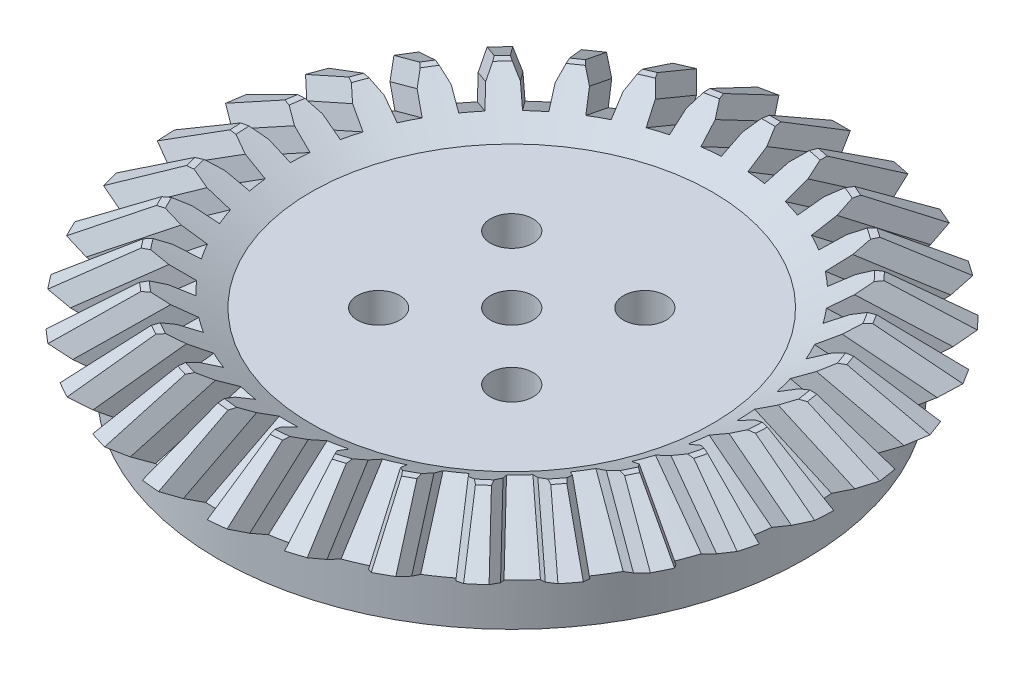
SolidWorks part; units mm, degrees
note: The reader was unsure of these and kept them because the rebuilt part matched: shared geometry of "Sketch13<3>".
ref_plane "Front Plane" through (0, 0, 0) normal (0, 0, 1) x (1, 0, 0)
ref_plane "Top Plane" through (0, 0, 0) normal (0, 1, 0) x (1, 0, 0)
ref_plane "Right Plane" through (0, 0, 0) normal (1, 0, 0) x (0, 0, -1)
sketch "Sketch1" plane through (0, 0, 0) normal (0, 1, 0) x (1, 0, 0)
  line L0 (0, 0) -> (-1.265, 22.0037) construction
  line L1 (0, 0) -> (1.265, 22.0037) construction
  line L2 (-1.265, 22.0037) -> (-1.265, 24.9437)
  line L3 (-1.265, 24.9437) -> (1.265, 24.9437) construction
  line L4 (1.265, 24.9437) -> (1.265, 22.0037)
  line L5 (-1.265, 24.9437) -> (-0.8171, 27.4837)
  line L6 (-0.8171, 27.4837) -> (0.8171, 27.4837)
  line L7 (0.8171, 27.4837) -> (1.265, 24.9437)
  line L8 (6.3328, 26.7566) -> (6.2602, 24.1784)
  line L9 (4.732, 27.0856) -> (6.3328, 26.7566)
  line L10 (3.782, 24.6877) -> (4.732, 27.0856)
  line L11 (3.1902, 21.8079) -> (3.782, 24.6877)
  line L12 (6.2602, 24.1784) -> (5.6684, 21.2986)
  line L13 (11.5893, 24.9341) -> (10.9992, 22.4233)
  line L14 (10.0874, 25.5786) -> (11.5893, 24.9341)
  line L15 (8.6742, 23.421) -> (10.0874, 25.5786)
  line L16 (7.5148, 20.7193) -> (8.6742, 23.421)
  line L17 (10.9992, 22.4233) -> (9.8398, 19.7216)
  line L18 (16.3712, 22.0908) -> (15.2878, 19.7502)
  line L19 (15.0299, 23.0244) -> (16.3712, 22.0908)
  line L20 (13.2113, 21.1955) -> (15.0299, 23.0244)
  line L21 (11.5317, 18.7825) -> (13.2113, 21.1955)
  line L22 (15.2878, 19.7502) -> (13.6083, 17.3372)
  line L23 (20.4829, 18.3431) -> (18.9505, 16.2685)
  line L24 (19.357, 19.5276) -> (20.4829, 18.3431)
  line L25 (17.2075, 18.1022) -> (19.357, 19.5276)
  line L26 (15.0766, 16.0767) -> (17.2075, 18.1022)
  line L27 (18.9505, 16.2685) -> (16.8196, 14.2429)
  line L28 (23.7561, 13.8444) -> (21.8374, 12.1208)
  line L29 (22.8916, 15.2313) -> (23.7561, 13.8444)
  line L30 (20.4992, 14.2678) -> (22.8916, 15.2313)
  line L31 (18.0042, 12.7127) -> (20.4992, 14.2678)
  line L32 (21.8374, 12.1208) -> (19.3424, 10.5656)
  line L33 (26.0567, 8.779) -> (23.8303, 7.4768)
  line L34 (25.4891, 10.3115) -> (26.0567, 8.779)
  line L35 (22.9516, 9.8493) -> (25.4891, 10.3115)
  line L36 (20.1947, 8.8282) -> (22.9516, 9.8493)
  line L37 (23.8303, 7.4768) -> (21.0733, 6.4557)
  line L38 (27.2905, 3.3541) -> (24.8476, 2.5268)
  line L39 (27.043, 4.9695) -> (27.2905, 3.3541)
  line L40 (24.4645, 5.0276) -> (27.043, 4.9695)
  line L41 (21.5584, 4.5824) -> (24.4645, 5.0276)
  line L42 (24.8476, 2.5268) -> (21.9415, 2.0816)
  line L43 (27.407, -2.2081) -> (24.8476, -2.5268)
  line L44 (27.4898, -0.5759) -> (27.407, -2.2081)
  line L45 (24.9757, 0) -> (27.4898, -0.5759)
  line L46 (22.0395, 0.1489) -> (24.9757, 0)
  line L47 (24.8476, -2.5268) -> (21.9114, -2.3778)
  line L48 (26.4015, -7.6799) -> (23.8303, -7.4768)
  line L49 (26.8111, -6.0978) -> (26.4015, -7.6799)
  line L50 (24.4645, -5.0276) -> (26.8111, -6.0978)
  line L51 (21.6183, -4.2907) -> (24.4645, -5.0276)
  line L52 (23.8303, -7.4768) -> (20.9842, -6.7399)
  line L53 (24.3151, -12.8373) -> (21.8374, -12.1208)
  line L54 (25.0348, -11.37) -> (24.3151, -12.8373)
  line L55 (22.9516, -9.8493) -> (25.0348, -11.37)
  line L56 (20.3121, -8.5546) -> (22.9516, -9.8493)
  line L57 (21.8374, -12.1208) -> (19.1979, -10.826)
  line L58 (21.2333, -17.4691) -> (18.9505, -16.2685)
  line L59 (22.2336, -16.1768) -> (21.2333, -17.4691)
  line L60 (20.4992, -14.2678) -> (22.2336, -16.1768)
  line L61 (18.1743, -12.4682) -> (20.4992, -14.2678)
  line L62 (18.9505, -16.2685) -> (16.6257, -14.4689)
  line L63 (17.2821, -21.3857) -> (15.2878, -19.7502)
  line L64 (18.5221, -20.3212) -> (17.2821, -21.3857)
  line L65 (17.2075, -18.1022) -> (18.5221, -20.3212)
  line L66 (15.2924, -15.8715) -> (17.2075, -18.1022)
  line L67 (15.2878, -19.7502) -> (13.3728, -17.5195)
  line L68 (12.6234, -24.4268) -> (10.9992, -22.4233)
  line L69 (14.0523, -23.6337) -> (12.6234, -24.4268)
  line L70 (13.2113, -21.1955) -> (14.0523, -23.6337)
  line L71 (11.7845, -18.6249) -> (13.2113, -21.1955)
  line L72 (10.9992, -22.4233) -> (9.5724, -19.8527)
  line L73 (7.4479, -26.4679) -> (6.2602, -24.1784)
  line L74 (9.0073, -25.9786) -> (7.4479, -26.4679)
  line L75 (8.6742, -23.421) -> (9.0073, -25.9786)
  line L76 (7.7941, -20.6159) -> (8.6742, -23.421)
  line L77 (6.2602, -24.1784) -> (5.3801, -21.3733)
  line L78 (1.9675, -27.4253) -> (1.265, -24.9437)
  line L79 (3.5934, -27.26) -> (1.9675, -27.4253)
  line L80 (3.782, -24.6877) -> (3.5934, -27.26)
  line L81 (3.4846, -21.7628) -> (3.782, -24.6877)
  line L82 (1.265, -24.9437) -> (0.9676, -22.0188)
  line L83 (-3.5934, -27.26) -> (-3.782, -24.6877)
  line L84 (-1.9675, -27.4253) -> (-3.5934, -27.26)
  line L85 (-1.265, -24.9437) -> (-1.9675, -27.4253)
  line L86 (-0.9676, -22.0188) -> (-1.265, -24.9437)
  line L87 (-3.782, -24.6877) -> (-3.4846, -21.7628)
  line L88 (-9.0073, -25.9786) -> (-8.6742, -23.421)
  line L89 (-7.4479, -26.4679) -> (-9.0073, -25.9786)
  line L90 (-6.2602, -24.1784) -> (-7.4479, -26.4679)
  line L91 (-5.3801, -21.3733) -> (-6.2602, -24.1784)
  line L92 (-8.6742, -23.421) -> (-7.7941, -20.6159)
  line L93 (-14.0523, -23.6337) -> (-13.2113, -21.1955)
  line L94 (-12.6234, -24.4268) -> (-14.0523, -23.6337)
  line L95 (-10.9992, -22.4233) -> (-12.6234, -24.4268)
  line L96 (-9.5724, -19.8527) -> (-10.9992, -22.4233)
  line L97 (-13.2113, -21.1955) -> (-11.7845, -18.6249)
  line L98 (-18.5221, -20.3212) -> (-17.2075, -18.1022)
  line L99 (-17.2821, -21.3857) -> (-18.5221, -20.3212)
  line L100 (-15.2878, -19.7502) -> (-17.2821, -21.3857)
  line L101 (-13.3728, -17.5195) -> (-15.2878, -19.7502)
  line L102 (-17.2075, -18.1022) -> (-15.2924, -15.8715)
  line L103 (-22.2336, -16.1768) -> (-20.4992, -14.2678)
  line L104 (-21.2333, -17.4691) -> (-22.2336, -16.1768)
  line L105 (-18.9505, -16.2685) -> (-21.2333, -17.4691)
  line L106 (-16.6257, -14.4689) -> (-18.9505, -16.2685)
  line L107 (-20.4992, -14.2678) -> (-18.1743, -12.4682)
  line L108 (0, 0) -> (2.2298, 21.9269) construction
  line L109 (3.1945, 21.8288) -> (1.265, 22.025) construction
  line L190 (-25.0348, -11.37) -> (-22.9516, -9.8493)
  line L191 (-24.3151, -12.8373) -> (-25.0348, -11.37)
  line L192 (-21.8374, -12.1208) -> (-24.3151, -12.8373)
  line L193 (-19.1979, -10.826) -> (-21.8374, -12.1208)
  line L194 (-22.9516, -9.8493) -> (-20.3121, -8.5546)
  line L195 (-26.8111, -6.0978) -> (-24.4645, -5.0276)
  line L196 (-26.4015, -7.6799) -> (-26.8111, -6.0978)
  line L197 (-23.8303, -7.4768) -> (-26.4015, -7.6799)
  line L198 (-20.9842, -6.7399) -> (-23.8303, -7.4768)
  line L199 (-24.4645, -5.0276) -> (-21.6183, -4.2907)
  line L200 (-27.4898, -0.5759) -> (-24.9757, 0)
  line L201 (-27.407, -2.2081) -> (-27.4898, -0.5759)
  line L202 (-24.8476, -2.5268) -> (-27.407, -2.2081)
  line L203 (-21.9114, -2.3778) -> (-24.8476, -2.5268)
  line L204 (-24.9757, 0) -> (-22.0395, 0.1489)
  line L205 (-27.043, 4.9695) -> (-24.4645, 5.0276)
  line L206 (-27.2905, 3.3541) -> (-27.043, 4.9695)
  line L207 (-24.8476, 2.5268) -> (-27.2905, 3.3541)
  line L208 (-21.9415, 2.0816) -> (-24.8476, 2.5268)
  line L209 (-24.4645, 5.0276) -> (-21.5584, 4.5824)
  line L210 (-25.4891, 10.3115) -> (-22.9516, 9.8493)
  line L211 (-26.0567, 8.779) -> (-25.4891, 10.3115)
  line L212 (-23.8303, 7.4768) -> (-26.0567, 8.779)
  line L213 (-21.0733, 6.4557) -> (-23.8303, 7.4768)
  line L214 (-22.9516, 9.8493) -> (-20.1947, 8.8282)
  line L215 (-22.8916, 15.2313) -> (-20.4992, 14.2678)
  line L216 (-23.7561, 13.8444) -> (-22.8916, 15.2313)
  line L217 (-21.8374, 12.1208) -> (-23.7561, 13.8444)
  line L218 (-19.3424, 10.5656) -> (-21.8374, 12.1208)
  line L219 (-20.4992, 14.2678) -> (-18.0042, 12.7127)
  line L220 (-19.357, 19.5276) -> (-17.2075, 18.1022)
  line L221 (-20.4829, 18.3431) -> (-19.357, 19.5276)
  line L222 (-18.9505, 16.2685) -> (-20.4829, 18.3431)
  line L223 (-16.8196, 14.2429) -> (-18.9505, 16.2685)
  line L224 (-17.2075, 18.1022) -> (-15.0766, 16.0767)
  line L225 (-15.0299, 23.0244) -> (-13.2113, 21.1955)
  line L226 (-16.3712, 22.0908) -> (-15.0299, 23.0244)
  line L227 (-15.2878, 19.7502) -> (-16.3712, 22.0908)
  line L228 (-13.6083, 17.3372) -> (-15.2878, 19.7502)
  line L229 (-13.2113, 21.1955) -> (-11.5317, 18.7825)
  line L230 (-10.0874, 25.5786) -> (-8.6742, 23.421)
  line L231 (-11.5893, 24.9341) -> (-10.0874, 25.5786)
  line L232 (-10.9992, 22.4233) -> (-11.5893, 24.9341)
  line L233 (-9.8398, 19.7216) -> (-10.9992, 22.4233)
  line L234 (-8.6742, 23.421) -> (-7.5148, 20.7193)
  line L235 (-4.732, 27.0856) -> (-3.782, 24.6877)
  line L236 (-6.3328, 26.7566) -> (-4.732, 27.0856)
  line L237 (-6.2602, 24.1784) -> (-6.3328, 26.7566)
  line L238 (-5.6684, 21.2986) -> (-6.2602, 24.1784)
  line L239 (-3.782, 24.6877) -> (-3.1902, 21.8079)
  line L245 (1.265, 24.9437) -> (3.782, 24.6877) construction
  arc A0 (-16.6257, -14.4689) -> (-15.2924, -15.8715) centre (0, 0) ccw
  arc A2 (3.1902, 21.8079) -> (1.265, 22.0037) centre (0, 0) ccw
  arc A3 (7.5148, 20.7193) -> (5.6684, 21.2986) centre (0, 0) ccw
  arc A4 (11.5317, 18.7825) -> (9.8398, 19.7216) centre (0, 0) ccw
  arc A5 (15.0766, 16.0767) -> (13.6083, 17.3372) centre (0, 0) ccw
  arc A6 (18.0042, 12.7127) -> (16.8196, 14.2429) centre (0, 0) ccw
  arc A7 (20.1947, 8.8282) -> (19.3424, 10.5656) centre (0, 0) ccw
  arc A8 (21.5584, 4.5824) -> (21.0733, 6.4557) centre (0, 0) ccw
  arc A9 (22.0395, 0.1489) -> (21.9415, 2.0816) centre (0, 0) ccw
  arc A10 (21.6183, -4.2907) -> (21.9114, -2.3778) centre (0, 0) ccw
  arc A11 (20.3121, -8.5546) -> (20.9842, -6.7399) centre (0, 0) ccw
  arc A12 (18.1743, -12.4682) -> (19.1979, -10.826) centre (0, 0) ccw
  arc A13 (15.2924, -15.8715) -> (16.6257, -14.4689) centre (0, 0) ccw
  arc A14 (11.7845, -18.6249) -> (13.3728, -17.5195) centre (0, 0) ccw
  arc A15 (7.7941, -20.6159) -> (9.5724, -19.8527) centre (0, 0) ccw
  arc A16 (3.4846, -21.7628) -> (5.3801, -21.3733) centre (0, 0) ccw
  arc A17 (-0.9676, -22.0188) -> (0.9676, -22.0188) centre (0, 0) ccw
  arc A18 (-5.3801, -21.3733) -> (-3.4846, -21.7628) centre (0, 0) ccw
  arc A19 (-9.5724, -19.8527) -> (-7.7941, -20.6159) centre (0, 0) ccw
  arc A20 (-13.3728, -17.5195) -> (-11.7845, -18.6249) centre (0, 0) ccw
  arc A36 (-18.1743, -12.4682) -> (-19.1979, -10.826) centre (0, 0) cw
  arc A69 (-7.5148, 20.7193) -> (-5.6684, 21.2986) centre (0, 0) cw
  arc A70 (-11.5317, 18.7825) -> (-9.8398, 19.7216) centre (0, 0) cw
  arc A71 (-15.0766, 16.0767) -> (-13.6083, 17.3372) centre (0, 0) cw
  arc A72 (-18.0042, 12.7127) -> (-16.8196, 14.2429) centre (0, 0) cw
  arc A73 (-20.1947, 8.8282) -> (-19.3424, 10.5656) centre (0, 0) cw
  arc A74 (-21.5584, 4.5824) -> (-21.0733, 6.4557) centre (0, 0) cw
  arc A75 (-22.0395, 0.1489) -> (-21.9415, 2.0816) centre (0, 0) cw
  arc A76 (-21.6183, -4.2907) -> (-21.9114, -2.3778) centre (0, 0) cw
  arc A77 (-20.3121, -8.5546) -> (-20.9842, -6.7399) centre (0, 0) cw
  arc A78 (-3.1902, 21.8079) -> (-1.265, 22.0037) centre (0, 0) cw
  circle A79 centre (0, 0) radius 27.4958 construction
  point P132 (0, 0)
  point P134 (2.2298, 21.9269)
  dimension "D1" = 2.53
  dimension "D7" = 54.9916
  dimension "D2" = 2.54
  dimension "D3" = 2.94
  dimension "D5" = 100
  dimension "D6" = 1.9395
  dimension "D9" = 95.806
  dimension "D10" = 2.53
  dimension "D11" = 1.9395
  dimension "D4" = 31
ref_plane "Plane1" through (0, 8, 0) normal (0, 1, 0) x (1, 0, 0)
sketch "Sketch10" plane through (0, 8, -4) normal (0, -1, 0) x (1, 0, 0)
  line L0 (0, 4) -> (-1.4366, 12.3944) construction
  line L1 (0, 4) -> (-0.2826, 12.5117) construction
  line L2 (-1.4366, 12.3944) -> (-1.734, 15.3193)
  line L3 (-1.734, 15.3193) -> (-0.58, 15.4366) construction
  line L4 (-0.58, 15.4366) -> (-0.2826, 12.5117)
  line L5 (-1.734, 15.3193) -> (-1.5454, 17.8915)
  line L6 (-1.5454, 17.8915) -> (-1.2825, 17.9183)
  line L7 (-1.2825, 17.9183) -> (-0.58, 15.4366)
  line L8 (1.5454, 17.8915) -> (1.734, 15.3193)
  line L9 (1.2825, 17.9183) -> (1.5454, 17.8915)
  line L10 (0.58, 15.4366) -> (1.2825, 17.9183)
  line L11 (0.2826, 12.5117) -> (0.58, 15.4366)
  line L12 (1.734, 15.3193) -> (1.4366, 12.3944)
  line L13 (4.3102, 17.2961) -> (3.9771, 14.7385)
  line L14 (4.058, 17.3752) -> (4.3102, 17.2961)
  line L15 (2.8703, 15.0858) -> (4.058, 17.3752)
  line L16 (1.9902, 12.2806) -> (2.8703, 15.0858)
  line L17 (3.9771, 14.7385) -> (3.097, 11.9333)
  line L18 (6.8984, 16.1563) -> (6.0573, 13.7181)
  line L19 (6.6674, 16.2845) -> (6.8984, 16.1563)
  line L20 (5.0431, 14.281) -> (6.6674, 16.2845)
  line L21 (3.6163, 11.7105) -> (5.0431, 14.281)
  line L22 (6.0573, 13.7181) -> (4.6306, 11.1475)
  line L23 (9.2042, 14.5188) -> (7.8896, 12.2998)
  line L24 (9.0037, 14.6909) -> (9.2042, 14.5188)
  line L25 (7.0094, 13.0554) -> (9.0037, 14.6909)
  line L26 (5.0944, 10.8247) -> (7.0094, 13.0554)
  line L27 (7.8896, 12.2998) -> (5.9745, 10.0691)
  line L28 (11.1333, 12.4507) -> (9.3988, 10.5418)
  line L29 (10.9715, 12.6597) -> (11.1333, 12.4507)
  line L30 (8.6888, 11.4591) -> (10.9715, 12.6597)
  line L31 (6.3639, 9.6595) -> (8.6888, 11.4591)
  line L32 (9.3988, 10.5418) -> (7.0739, 8.7422)
  line L33 (12.6065, 10.0366) -> (10.5233, 8.5159)
  line L34 (12.4901, 10.2739) -> (12.6065, 10.0366)
  line L35 (10.0124, 9.5573) -> (12.4901, 10.2739)
  line L36 (7.3729, 8.2626) -> (10.0124, 9.5573)
  line L37 (10.5233, 8.5159) -> (7.8837, 7.2211)
  line L38 (13.5636, 7.3754) -> (11.2169, 6.3051)
  line L39 (13.4973, 7.6312) -> (13.5636, 7.3754)
  line L40 (10.9262, 7.4281) -> (13.4973, 7.6312)
  line L41 (8.08, 6.6912) -> (10.9262, 7.4281)
  line L42 (11.2169, 6.3051) -> (8.3708, 5.5682)
  line L43 (13.9654, 4.5759) -> (11.4513, 4)
  line L44 (13.952, 4.8399) -> (13.9654, 4.5759)
  line L45 (11.3926, 5.1585) -> (13.952, 4.8399)
  line L46 (8.4563, 5.0096) -> (11.3926, 5.1585)
  line L47 (11.4513, 4) -> (8.5151, 3.8511)
  line L48 (13.7954, 1.7529) -> (11.2169, 1.6949)
  line L49 (13.8355, 2.0142) -> (13.7954, 1.7529)
  line L50 (11.3926, 2.8415) -> (13.8355, 2.0142)
  line L51 (8.4865, 3.2867) -> (11.3926, 2.8415)
  line L52 (11.2169, 1.6949) -> (8.3108, 2.1401)
  line L53 (13.0607, -0.9781) -> (10.5233, -0.5159)
  line L54 (13.1525, -0.7303) -> (13.0607, -0.9781)
  line L55 (10.9262, 0.5719) -> (13.1525, -0.7303)
  line L56 (8.1692, 1.593) -> (10.9262, 0.5719)
  line L57 (10.5233, -0.5159) -> (7.7663, 0.5052)
  line L58 (11.7913, -3.5053) -> (9.3988, -2.5418)
  line L59 (11.9311, -3.281) -> (11.7913, -3.5053)
  line L60 (10.0124, -1.5573) -> (11.9311, -3.281)
  line L61 (7.5174, -0.0022) -> (10.0124, -1.5573)
  line L62 (9.3988, -2.5418) -> (6.9038, -0.9866)
  line L63 (10.0391, -5.7252) -> (7.8896, -4.2998)
  line L64 (10.2212, -5.5337) -> (10.0391, -5.7252)
  line L65 (8.6888, -3.4591) -> (10.2212, -5.5337)
  line L66 (6.5579, -1.4335) -> (8.6888, -3.4591)
  line L67 (7.8896, -4.2998) -> (5.7587, -2.2743)
  line L68 (7.876, -7.547) -> (6.0573, -5.7181)
  line L69 (8.0928, -7.396) -> (7.876, -7.547)
  line L70 (7.0094, -5.0554) -> (8.0928, -7.396)
  line L71 (5.3299, -2.6424) -> (7.0094, -5.0554)
  line L72 (6.0573, -5.7181) -> (4.3778, -3.3051)
  line L73 (5.3903, -8.896) -> (3.9771, -6.7385)
  line L74 (5.6332, -8.7918) -> (5.3903, -8.896)
  line L75 (5.0431, -6.281) -> (5.6332, -8.7918)
  line L76 (3.8837, -3.5793) -> (5.0431, -6.281)
  line L77 (3.9771, -6.7385) -> (2.8177, -4.0368)
  line L78 (2.684, -9.7171) -> (1.734, -7.3193)
  line L79 (2.9429, -9.6639) -> (2.684, -9.7171)
  line L80 (2.8703, -7.0858) -> (2.9429, -9.6639)
  line L81 (2.2785, -4.2059) -> (2.8703, -7.0858)
  line L82 (1.734, -7.3193) -> (1.1422, -4.4395)
  line L83 (-0.1321, -9.9766) -> (-0.58, -7.4366)
  line L84 (0.1321, -9.9766) -> (-0.1321, -9.9766)
  line L85 (0.58, -7.4366) -> (0.1321, -9.9766)
  line L86 (0.58, -4.4966) -> (0.58, -7.4366)
  line L87 (-0.58, -7.4366) -> (-0.58, -4.4966)
  line L88 (-2.9429, -9.6639) -> (-2.8703, -7.0858)
  line L89 (-2.684, -9.7171) -> (-2.9429, -9.6639)
  line L90 (-1.734, -7.3193) -> (-2.684, -9.7171)
  line L91 (-1.1422, -4.4395) -> (-1.734, -7.3193)
  line L92 (-2.8703, -7.0858) -> (-2.2785, -4.2059)
  line L93 (-5.6332, -8.7918) -> (-5.0431, -6.281)
  line L94 (-5.3903, -8.896) -> (-5.6332, -8.7918)
  line L95 (-3.9771, -6.7385) -> (-5.3903, -8.896)
  line L96 (-2.8177, -4.0368) -> (-3.9771, -6.7385)
  line L97 (-5.0431, -6.281) -> (-3.8837, -3.5793)
  line L98 (-8.0928, -7.396) -> (-7.0094, -5.0554)
  line L99 (-7.876, -7.547) -> (-8.0928, -7.396)
  line L100 (-6.0573, -5.7181) -> (-7.876, -7.547)
  line L101 (-4.3778, -3.3051) -> (-6.0573, -5.7181)
  line L102 (-7.0094, -5.0554) -> (-5.3299, -2.6424)
  line L103 (-10.2212, -5.5337) -> (-8.6888, -3.4591)
  line L104 (-10.0391, -5.7252) -> (-10.2212, -5.5337)
  line L105 (-7.8896, -4.2998) -> (-10.0391, -5.7252)
  line L106 (-5.7587, -2.2743) -> (-7.8896, -4.2998)
  line L107 (-8.6888, -3.4591) -> (-6.5579, -1.4335)
  line L108 (0, 4) -> (0, 12.5164) construction
  line L109 (0.283, 12.5164) -> (-0.283, 12.5164) construction
  line L190 (-11.9311, -3.281) -> (-10.0124, -1.5573)
  line L191 (-11.7913, -3.5053) -> (-11.9311, -3.281)
  line L192 (-9.3988, -2.5418) -> (-11.7913, -3.5053)
  line L193 (-6.9038, -0.9866) -> (-9.3988, -2.5418)
  line L194 (-10.0124, -1.5573) -> (-7.5174, -0.0022)
  line L195 (-13.1525, -0.7303) -> (-10.9262, 0.5719)
  line L196 (-13.0607, -0.9781) -> (-13.1525, -0.7303)
  line L197 (-10.5233, -0.5159) -> (-13.0607, -0.9781)
  line L198 (-7.7663, 0.5052) -> (-10.5233, -0.5159)
  line L199 (-10.9262, 0.5719) -> (-8.1692, 1.593)
  line L200 (-13.8355, 2.0142) -> (-11.3926, 2.8415)
  line L201 (-13.7954, 1.7529) -> (-13.8355, 2.0142)
  line L202 (-11.2169, 1.6949) -> (-13.7954, 1.7529)
  line L203 (-8.3108, 2.1401) -> (-11.2169, 1.6949)
  line L204 (-11.3926, 2.8415) -> (-8.4865, 3.2867)
  line L205 (-13.952, 4.8399) -> (-11.3926, 5.1585)
  line L206 (-13.9654, 4.5759) -> (-13.952, 4.8399)
  line L207 (-11.4513, 4) -> (-13.9654, 4.5759)
  line L208 (-8.5151, 3.8511) -> (-11.4513, 4)
  line L209 (-11.3926, 5.1585) -> (-8.4563, 5.0096)
  line L210 (-13.4973, 7.6312) -> (-10.9262, 7.4281)
  line L211 (-13.5636, 7.3754) -> (-13.4973, 7.6312)
  line L212 (-11.2169, 6.3051) -> (-13.5636, 7.3754)
  line L213 (-8.3708, 5.5682) -> (-11.2169, 6.3051)
  line L214 (-10.9262, 7.4281) -> (-8.08, 6.6912)
  line L215 (-12.4901, 10.2739) -> (-10.0124, 9.5573)
  line L216 (-12.6065, 10.0366) -> (-12.4901, 10.2739)
  line L217 (-10.5233, 8.5159) -> (-12.6065, 10.0366)
  line L218 (-7.8837, 7.2211) -> (-10.5233, 8.5159)
  line L219 (-10.0124, 9.5573) -> (-7.3729, 8.2626)
  line L220 (-10.9715, 12.6597) -> (-8.6888, 11.4591)
  line L221 (-11.1333, 12.4507) -> (-10.9715, 12.6597)
  line L222 (-9.3988, 10.5418) -> (-11.1333, 12.4507)
  line L223 (-7.0739, 8.7422) -> (-9.3988, 10.5418)
  line L224 (-8.6888, 11.4591) -> (-6.3639, 9.6595)
  line L225 (-9.0037, 14.6909) -> (-7.0094, 13.0554)
  line L226 (-9.2042, 14.5188) -> (-9.0037, 14.6909)
  line L227 (-7.8896, 12.2998) -> (-9.2042, 14.5188)
  line L228 (-5.9745, 10.0691) -> (-7.8896, 12.2998)
  line L229 (-7.0094, 13.0554) -> (-5.0944, 10.8247)
  line L230 (-6.6674, 16.2845) -> (-5.0431, 14.281)
  line L231 (-6.8984, 16.1563) -> (-6.6674, 16.2845)
  line L232 (-6.0573, 13.7181) -> (-6.8984, 16.1563)
  line L233 (-4.6306, 11.1475) -> (-6.0573, 13.7181)
  line L234 (-5.0431, 14.281) -> (-3.6163, 11.7105)
  line L235 (-4.058, 17.3752) -> (-2.8703, 15.0858)
  line L236 (-4.3102, 17.2961) -> (-4.058, 17.3752)
  line L237 (-3.9771, 14.7385) -> (-4.3102, 17.2961)
  line L238 (-3.097, 11.9333) -> (-3.9771, 14.7385)
  line L239 (-2.8703, 15.0858) -> (-1.9902, 12.2806)
  line L395 (59.5854, -8.896) -> (65.5711, -8.896)
  line L396 (65.5711, -8.896) -> (65.5711, -5.4038)
  line L397 (65.5711, -5.4038) -> (59.5854, -8.896)
  line L398 (42.9603, -11.0104) -> (42.9603, -19.0104)
  line L399 (42.9603, -19.0104) -> (38.3415, -19.0104)
  line L400 (38.3415, -19.0104) -> (42.9603, -11.0104)
  line L401 (42.564, -21.8479) -> (45.764, -21.8479)
  line L402 (45.764, -21.8479) -> (50.4314, -29.8479)
  line L403 (50.4314, -29.8479) -> (47.2314, -29.8479)
  line L404 (47.2314, -29.8479) -> (42.564, -21.8479)
  line L405 (39.9454, -30.2426) -> (45.4224, -30.2426)
  line L406 (45.4224, -30.2426) -> (51.3702, -33.7126)
  line L407 (51.3702, -33.7126) -> (45.8931, -33.7126)
  line L408 (45.8931, -33.7126) -> (39.9454, -30.2426)
  line L409 (45.1553, -19.0104) -> (59.0117, -19.0104)
  line L410 (59.0117, -19.0104) -> (59.0117, -11.0104)
  line L411 (59.0117, -11.0104) -> (45.1553, -19.0104)
  line L412 (-0.58, 15.4366) -> (0.58, 15.4366) construction
  line L413 (-1.9675, 31.4253) -> (-3.5934, 31.26) construction
  line L414 (37.5887, 7.2511) -> (40.1187, 7.2511)
  line L415 (40.1187, 7.2511) -> (39.4337, 23.2511)
  line L416 (39.4337, 23.2511) -> (38.2737, 23.2511)
  line L417 (38.2737, 23.2511) -> (37.5887, 7.2511)
  line L418 (45.8813, 7.2511) -> (48.4113, 7.2511)
  line L419 (48.4113, 7.2511) -> (48.0163, 16.4911)
  line L420 (48.0163, 16.4911) -> (46.2763, 16.4911)
  line L421 (46.2763, 16.4911) -> (45.8813, 7.2511)
  line L422 (46.0096, 10.2511) -> (48.2831, 10.2511)
  line L423 (37.7169, 10.2466) -> (39.9904, 10.2466)
  line L424 (37.9843, 16.4911) -> (39.7231, 16.4911)
  arc A0 (-5.7587, -2.2743) -> (-5.3299, -2.6424) centre (0, 4) ccw
  arc A2 (0.2826, 12.5117) -> (-0.2826, 12.5117) centre (0, 4) ccw
  arc A3 (1.9902, 12.2806) -> (1.4366, 12.3944) centre (0, 4) ccw
  arc A4 (3.6163, 11.7105) -> (3.097, 11.9333) centre (0, 4) ccw
  arc A5 (5.0944, 10.8247) -> (4.6306, 11.1475) centre (0, 4) ccw
  arc A6 (6.3639, 9.6595) -> (5.9745, 10.0691) centre (0, 4) ccw
  arc A7 (7.3729, 8.2626) -> (7.0739, 8.7422) centre (0, 4) ccw
  arc A8 (8.08, 6.6912) -> (7.8837, 7.2211) centre (0, 4) ccw
  arc A9 (8.4563, 5.0096) -> (8.3708, 5.5682) centre (0, 4) ccw
  arc A10 (8.4865, 3.2867) -> (8.5151, 3.8511) centre (0, 4) ccw
  arc A11 (8.1692, 1.593) -> (8.3108, 2.1401) centre (0, 4) ccw
  arc A12 (7.5174, -0.0022) -> (7.7663, 0.5052) centre (0, 4) ccw
  arc A13 (6.5579, -1.4335) -> (6.9038, -0.9866) centre (0, 4) ccw
  arc A14 (5.3299, -2.6424) -> (5.7587, -2.2743) centre (0, 4) ccw
  arc A15 (3.8837, -3.5793) -> (4.3778, -3.3051) centre (0, 4) ccw
  arc A16 (2.2785, -4.2059) -> (2.8177, -4.0368) centre (0, 4) ccw
  arc A17 (0.58, -4.4966) -> (1.1422, -4.4395) centre (0, 4) ccw
  arc A18 (-1.1422, -4.4395) -> (-0.58, -4.4966) centre (0, 4) ccw
  arc A19 (-2.8177, -4.0368) -> (-2.2785, -4.2059) centre (0, 4) ccw
  arc A20 (-4.3778, -3.3051) -> (-3.8837, -3.5793) centre (0, 4) ccw
  arc A36 (-6.5579, -1.4335) -> (-6.9038, -0.9866) centre (0, 4) cw
  arc A69 (-3.6163, 11.7105) -> (-3.097, 11.9333) centre (0, 4) cw
  arc A70 (-5.0944, 10.8247) -> (-4.6306, 11.1475) centre (0, 4) cw
  arc A71 (-6.3639, 9.6595) -> (-5.9745, 10.0691) centre (0, 4) cw
  arc A72 (-7.3729, 8.2626) -> (-7.0739, 8.7422) centre (0, 4) cw
  arc A73 (-8.08, 6.6912) -> (-7.8837, 7.2211) centre (0, 4) cw
  arc A74 (-8.4563, 5.0096) -> (-8.3708, 5.5682) centre (0, 4) cw
  arc A75 (-8.4865, 3.2867) -> (-8.5151, 3.8511) centre (0, 4) cw
  arc A76 (-8.1692, 1.593) -> (-8.3108, 2.1401) centre (0, 4) cw
  arc A77 (-7.5174, -0.0022) -> (-7.7663, 0.5052) centre (0, 4) cw
  circle A80 centre (0, 4) radius 13.9773 construction
  arc A81 (-1.9902, 12.2806) -> (-1.4366, 12.3944) centre (0, 4) cw
  point P132 (0, 4)
  point P134 (0, 12.5164)
  dimension "D7" = 6.93
  dimension "D14" = 9.2376
  dimension "D8" = 8
  dimension "D9" = 27.9545
  dimension "D13" = 1.16
  dimension "D19" = 0.5661
  dimension "D2" = 2.54
  dimension "D3" = 2.94
  dimension "D5" = 100
  dimension "D6" = 30.26
  dimension "D10" = 60
  dimension "D11" = 4.6188
  dimension "D12" = 5.9858
  dimension "D15" = 3.4922
  dimension "D16" = 8
  dimension "D17" = 59.74
  dimension "D18" = 3.2
  dimension "D20" = 2.764
  dimension "D21" = 30.26
  dimension "D22" = 3.47
  dimension "D23" = 2.76
  dimension "D24" = 5.477
  dimension "D25" = 8.5164
  dimension "D26" = 30
  dimension "D27" = 8
  dimension "D28" = 13.8564
  dimension "D29" = 2.53
  dimension "D30" = 16
  dimension "D31" = 1.16
  dimension "D32" = 1.74
  dimension "D33" = 9.24
  dimension "D34" = 3
  dimension "D35" = 6.24
  dimension "D36" = 2.53
  dimension "D37" = 2.2735
  dimension "D38" = 87.549
  dimension "D39" = 87.552
  dimension "D40" = 2.9955
  dimension "D41" = 6.76
  dimension "D42" = 1.7388
  dimension "D4" = 31
loft "Loft2" add profiles "Sketch1" section "Sketch1" section "Sketch10"
sketch "Sketch11" plane through (0, 0, 0) normal (0, 0, 1) x (1, 0, 0)
  line L0 (0, 0) -> (27.55, 0)
  line L4 (0, 0) -> (0, 8)
  line L5 (0, 8) -> (25.2382, 8)
  line L6 (25.2382, 8) -> (15.0754, 2.1325)
  line L7 (17.2821, 0) -> (9.0037, 8) construction
  line L10 (15.0754, 2.1325) -> (0, 2.1325)
  line L11 (27.55, 0) -> (24.7985, 1.6337)
  line L18 (24.7985, 1.6337) -> (22.0469, 0)
  line L19 (23.8303, 0) -> (26.4015, 0) construction
  line L20 (19.5792, 4.7327) -> (24.7985, 1.6337) construction
  line L21 (19.5792, 4.7327) -> (19.875, 4.5571)
  line L22 (19.875, 4.5571) -> (19.275, 4.5571)
  line L30 (45.7535, 5.078) -> (45.7535, 13.078)
  line L35 (45.7535, 13.078) -> (31.8971, 5.078)
  line L36 (31.8971, 5.078) -> (45.7535, 5.078)
  line L41 (59.1286, 5.078) -> (63.7474, 5.078)
  line L42 (63.7474, 5.078) -> (63.7474, 13.078)
  line L43 (63.7474, 13.078) -> (59.1286, 5.078)
  line L48 (41.858, -27.2391) -> (44.388, -27.2391)
  line L49 (44.388, -27.2391) -> (43.703, -11.2391)
  line L50 (43.703, -11.2391) -> (42.543, -11.2391)
  line L51 (42.543, -11.2391) -> (41.858, -27.2391)
  line L52 (50.1507, -27.2391) -> (52.6807, -27.2391)
  line L53 (52.6807, -27.2391) -> (52.2857, -17.9991)
  line L54 (52.2857, -17.9991) -> (50.5457, -17.9991)
  line L55 (50.5457, -17.9991) -> (50.1507, -27.2391)
  line L56 (50.279, -24.2391) -> (52.5525, -24.2391)
  line L57 (41.9863, -24.2436) -> (44.2598, -24.2436)
  line L58 (42.2536, -17.9991) -> (43.9925, -17.9991)
  point P38 (25.3943, 8)
  point P39 (25.108, 1.8175)
  point P40 (0, 0)
  point P41 (0, 0)
  dimension "D1" = 27.55
  dimension "D2" = 30.7
  dimension "D3" = 3.2
  dimension "D4" = 8
  dimension "D5" = 150
  dimension "D6" = 6.07
  dimension "D7" = 30
  dimension "D8" = 8
  dimension "D9" = 0.6
  dimension "D10" = 16
  dimension "D11" = 2.53
  dimension "D12" = 16
  dimension "D13" = 1.16
  dimension "D14" = 60
  dimension "D15" = 9.2376
  dimension "D16" = 1.74
  dimension "D17" = 9.24
  dimension "D18" = 3
  dimension "D19" = 6.24
  dimension "D20" = 2.53
  dimension "D21" = 2.2735
  dimension "D22" = 87.549
  dimension "D23" = 87.552
  dimension "D24" = 2.9955
  dimension "D25" = 1.7388
  dimension "D26" = 6.76
  dimension "D27" = 6.2445
revolve "Cut-Revolve1" cut sketch "Sketch11" angle 360 about L4
sketch "Sketch12" plane through (0, 0, 0) normal (0, -1, 0) x (1, 0, 0)
  circle A0 centre (0, 0) radius 22.04
  arc A1 (5.3801, 21.3733) -> (3.4846, 21.7628) centre (0, 0) ccw construction
extrude "Boss-Extrude1" add sketch "Sketch12" along normal blind 3.2
sketch "Sketch13" plane through (0, -3.2, 0) normal (0, -1, 0) x (1, 0, 0)
  line L0 (-5, 5) -> (-9.4265, 9.4265) construction
  line L1 (-5, -5) -> (5, -5) construction
  line L2 (-5, -5) -> (-5, 5) construction
  line L3 (-5, 5) -> (5, 5) construction
  line L4 (5, -5) -> (5, 5) construction
  line L5 (-5, -5) -> (5, 5) construction
  line L6 (-5, 5) -> (5, -5) construction
  circle A0 centre (-5, 5) radius 1.6
  circle A1 centre (5, 5) radius 1.6
  circle A2 centre (5, -5) radius 1.6
  circle A3 centre (-5, -5) radius 1.6
  circle A4 centre (0, 0) radius 1.6
  circle A5 centre (0, 0) radius 13.3311 construction
  circle A6 centre (0, 0) radius 11.3311
  circle A7 centre (0, 0) radius 15.3311
  point P0 (0, 0)
  dimension "D1" = 3.2
  dimension "D3" = 6.26
  dimension "D4" = 2
  dimension "D5" = 2
  dimension "D6" = 22.6621
  dimension "D2" = 10
extrude "Cut-Extrude1" cut sketch "Sketch13" against normal up to surface (5.3325 mm away) contours A0 | A1 | A2 | A3 | A4 up to face at (0, 2.1325, -15.0754)
extrude "Cut-Extrude2" cut sketch "Sketch13<3>" against normal blind 3 contours A7 A6
sketch "Sketch13<3>" plane through (0, -3.2, 0) normal (0, -1, 0) x (1, 0, 0) same geometry as "Sketch13"
chamfer "Chamfer1" [suppressed] distance 2 angle 45
chamfer "Chamfer2" [suppressed] distance 4.1 angle 45
